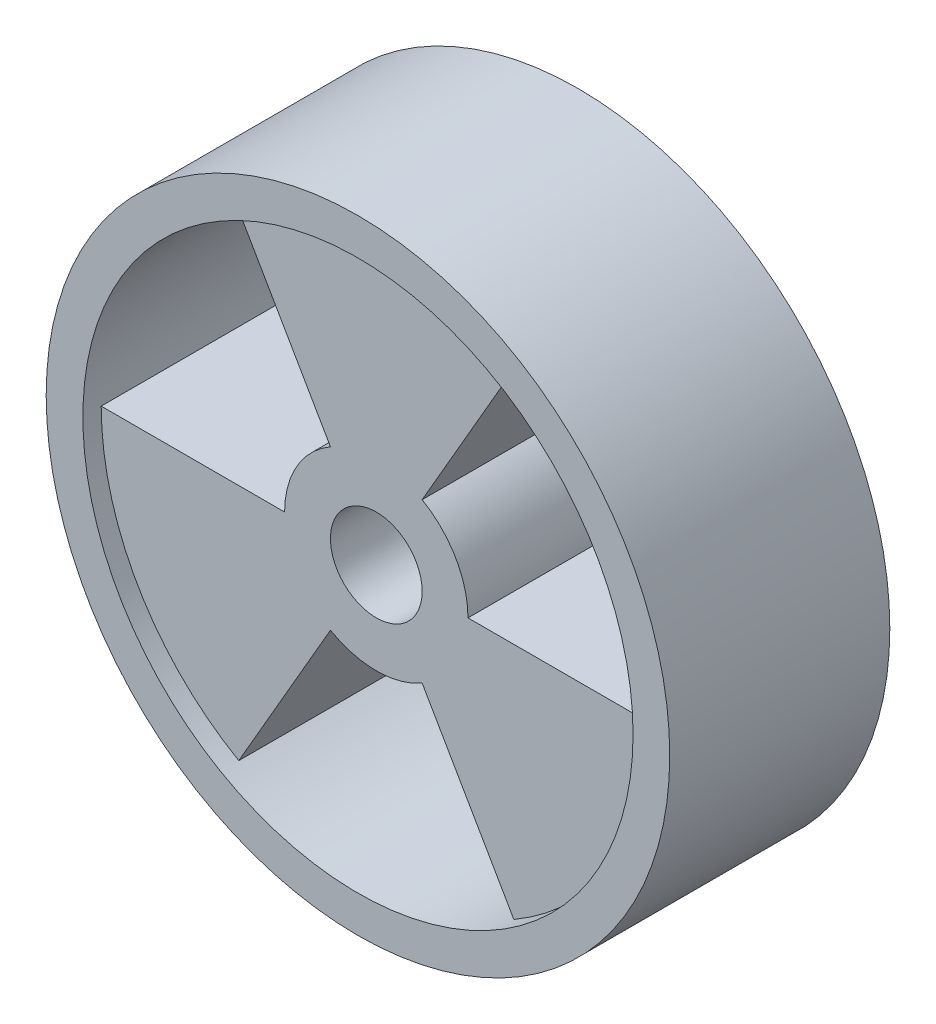
SolidWorks part; units mm, degrees
ref_plane "Front Plane" through (0, 0, 0) normal (0, 0, 1) x (1, 0, 0)
ref_plane "Top Plane" through (0, 0, 0) normal (0, 1, 0) x (1, 0, 0)
ref_plane "Right Plane" through (0, 0, 0) normal (1, 0, 0) x (0, 0, -1)
sketch "Sketch1" plane through (0, 0, 0) normal (0, 0, 1) x (1, 0, 0)
  line L0 (2.5, 4.3301) -> (7.5, 12.9904)
  line L1 (-2.5, 4.3301) -> (-7.5, 12.9904)
  line L2 (2.5, -4.3301) -> (7.5, -12.9904)
  line L3 (5, 0) -> (15, 0)
  line L4 (-5, 0) -> (-15, 0)
  line L5 (-2.5, -4.3301) -> (-7.5, -12.9904)
  circle A0 centre (0, 0) radius 17
  circle A1 centre (0, 0) radius 15
  circle A2 centre (0, 0) radius 5
  circle A3 centre (0, 0) radius 2.5
  point P20 (0, 0)
  dimension "D3" = 30
  dimension "D5" = 34
  dimension "D4" = 5
  dimension "D6" = 3
  dimension "D1" = 10
  dimension "D7" = 5
  dimension "D2" = 60
extrude "Boss-Extrude1" add sketch "Sketch1" along normal blind 10 contours A0
extrude "Cut-Extrude2" cut sketch "Sketch1<5>" along normal up to next contours A2 L3 A1 L0 | A2 L5 A1 L2 | A2 L1 A1 L4 region at (8.9591, 5.1725, 0) region at (-8.9591, 5.1725, 0) region at (0, -10.3451, 0)
sketch "Sketch1<5>" plane through (0, 0, 0) normal (0, 0, 1) x (1, 0, 0) same geometry as "Sketch1"
extrude "Boss-Extrude2" add sketch "Sketch1<6>" along normal blind 11 and the other way blind 1 contours A0 A1 region at (-16.5192, 0, 0)
sketch "Sketch1<6>" plane through (0, 0, 0) normal (0, 0, 1) x (1, 0, 0) same geometry as "Sketch1"
extrude "Cut-Extrude3" cut sketch "Sketch1<7>" along normal up to next contours A3
sketch "Sketch1<7>" plane through (0, 0, 0) normal (0, 0, 1) x (1, 0, 0) same geometry as "Sketch1"
